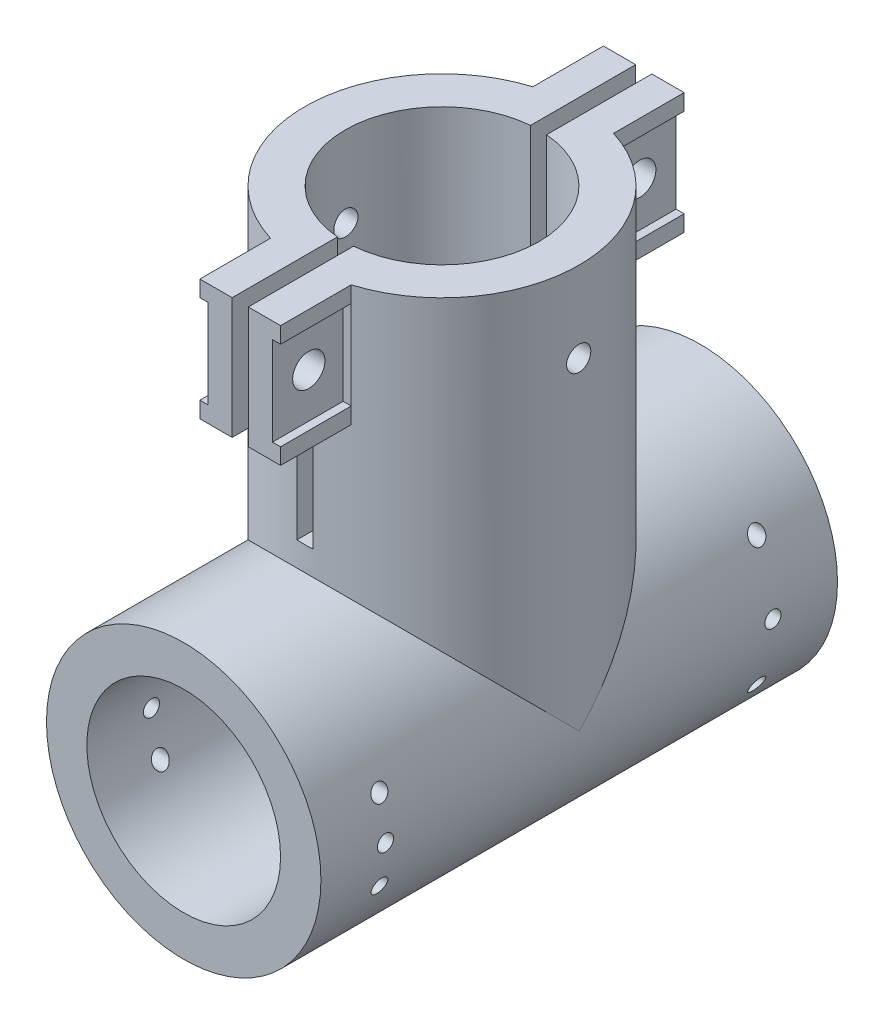
SolidWorks part; units mm, degrees
ref_plane "Front Plane" through (0, 0, 0) normal (0, 0, 1) x (1, 0, 0)
ref_plane "Top Plane" through (0, 0, 0) normal (0, 1, 0) x (1, 0, 0)
ref_plane "Right Plane" through (0, 0, 0) normal (1, 0, 0) x (0, 0, -1)
sketch "Sketch1" plane through (0, 0, 0) normal (0, 0, 1) x (1, 0, 0)
  circle A0 centre (-32.2971, 4.4232) radius 17
  circle A1 centre (-32.2971, 4.4232) radius 12
  dimension "D1" = 34
  dimension "D2" = 5
extrude "Boss-Extrude1" add sketch "Sketch1" along normal blind 64
ref_axis "Axis2" through (-32.2971, 4.4232, 64) along (0, 0, -1)
ref_plane "Plane1" through (0, 4.4232, 0) normal (0, 1, 0) x (1, 0, 0)
sketch "Sketch2" plane through (0, 4.4232, 0) normal (0, 1, 0) x (1, 0, 0)
  line L0 (-32.2971, -64) -> (-32.2971, 0) construction
  line L1 (-15.2971, 0) -> (-49.2971, 0) construction
  circle A0 centre (-32.2971, -32) radius 17
  circle A1 centre (-32.2971, -32) radius 12
  dimension "D1" = 32
  dimension "D2" = 5
  dimension "D3" = 34
extrude "Boss-Extrude2" add sketch "Sketch2" along normal blind 50
sketch "Sketch3" plane through (0, 0, 64) normal (0, 0, 1) x (1, 0, 0)
  circle A0 centre (-32.2971, 4.4232) radius 12
extrude "Cut-Extrude1" cut sketch "Sketch3" against normal through all
sketch "Sketch6" plane through (0, 54.4232, 0) normal (0, 1, 0) x (1, 0, 0)
  circle A0 centre (-32.2971, -32) radius 12
ref_axis "Axis3" through (-32.2971, 54.4232, 32) along (0, -1, 0)
ref_plane "Plane2" through (0, 0, 32) normal (0, 0, -1) x (-1, 0, 0)
sketch "Sketch4" plane through (0, 0, 32) normal (0, 0, -1) x (-1, 0, 0)
  line L0 (49.2971, 54.4232) -> (15.2971, 54.4232) construction
  line L1 (37.2971, 54.4232) -> (27.2971, 54.4232)
  line L2 (37.2971, 54.4232) -> (37.2971, 39.4232)
  line L3 (37.2971, 39.4232) -> (27.2971, 39.4232)
  line L4 (27.2971, 54.4232) -> (27.2971, 39.4232)
  line L5 (32.2971, 54.4232) -> (32.2971, 15.582) construction
  dimension "D1" = 10
  dimension "D2" = 5
  dimension "D3" = 15
extrude "Boss-Extrude3" add sketch "Sketch4" along normal mid plane 50
sketch "Sketch5" plane through (0, 0, 57) normal (0, 0, 1) x (1, 0, 0)
  line L0 (-37.2971, 54.4232) -> (-27.2971, 54.4232) construction
  line L1 (-33.2971, 54.4232) -> (-31.2971, 54.4232)
  line L2 (-33.2971, 54.4232) -> (-33.2971, 24.4232)
  line L3 (-33.2971, 24.4232) -> (-31.2971, 24.4232)
  line L4 (-31.2971, 54.4232) -> (-31.2971, 24.4232)
  line L5 (-32.2971, 54.4232) -> (-32.2971, 15.582) construction
  dimension "D1" = 2
  dimension "D2" = 1
  dimension "D3" = 30
extrude "Cut-Extrude2" cut sketch "Sketch5" against normal blind 50
extrude "Cut-Extrude3" cut sketch "Sketch6" against normal blind 50
sketch "Sketch7" plane through (-27.2971, 0, 0) normal (1, 0, 0) x (0, 0, -1)
  line L0 (-57, 54.4232) -> (-57, 39.4232) construction
  line L1 (-57, 52.4232) -> (-48.2481, 52.4232)
  line L2 (-57, 52.4232) -> (-57, 41.4232)
  line L3 (-57, 41.4232) -> (-48.2481, 41.4232)
  line L4 (-48.2481, 52.4232) -> (-48.2481, 41.4232)
  line L5 (-48.2481, 39.4232) -> (-48.2481, 54.4232) construction
  line L6 (-15.7519, 54.4232) -> (-15.7519, 39.4232) construction
  line L7 (-15.7519, 52.4232) -> (-7, 52.4232)
  line L8 (-15.7519, 52.4232) -> (-15.7519, 41.4232)
  line L9 (-15.7519, 41.4232) -> (-7, 41.4232)
  line L10 (-7, 52.4232) -> (-7, 41.4232)
  line L11 (-7, 54.4232) -> (-7, 39.4232) construction
  line L12 (-48.2481, 54.4232) -> (-57, 54.4232) construction
  line L13 (-48.2481, 39.4232) -> (-57, 39.4232) construction
  line L14 (-7, 54.4232) -> (-15.7519, 54.4232) construction
  line L15 (-7, 39.4232) -> (-15.7519, 39.4232) construction
  dimension "D1" = 2
  dimension "D2" = 2
  dimension "D3" = 2
  dimension "D4" = 2
extrude "Kes-Ekstrüzyon4" cut sketch "Sketch7" against normal blind 1
sketch "Sketch8" plane through (-28.2971, 0, 0) normal (1, 0, 0) x (0, 0, -1)
  line L0 (-7, 54.4232) -> (-15.7519, 54.4232) construction
  line L1 (-57, 52.4232) -> (-57, 41.4232) construction
  line L4 (-7, 41.4232) -> (-7, 52.4232) construction
  line L5 (-43.9583, 54.4232) -> (-57, 54.4232) construction
  circle A0 centre (-52.5, 46.9232) radius 2
  circle A1 centre (-11.5, 46.9232) radius 2
  point P6 (-57, 46.9232)
  dimension "D1" = 4
  dimension "D2" = 4
  dimension "D3" = 4.5
  dimension "D4" = 4.5
  dimension "D5" = 7.5
  dimension "D6" = 7.5
extrude "Cut-Extrude5" cut sketch "Sketch8" against normal through all
ref_plane "Plane3" through (-15.2971, 0, 0) normal (1, 0, 0) x (0, 0, -1)
sketch "Sketch9" plane through (-15.2971, 0, 0) normal (1, 0, 0) x (0, 0, -1)
  line L0 (35.2, 4.4232) -> (-35.2, 4.4232) construction
  line L1 (-64, 4.4232) -> (0, 4.4232) construction
  line L2 (-64, 21.4232) -> (-64, -12.5768) construction
  line L3 (0, -12.5768) -> (0, 21.4232) construction
  line L4 (-32, -27.5) -> (-32, 27.5) construction
  line L5 (-15.7519, 54.4232) -> (-48.2481, 54.4232) construction
  circle A0 centre (-56, 4.4232) radius 1
  circle A1 centre (-56, 9.4232) radius 1
  circle A2 centre (-56, -0.5768) radius 1
  circle A3 centre (-8, 4.4232) radius 1
  circle A4 centre (-8, 12.4232) radius 1
  circle A5 centre (-8, -3.5768) radius 1
  circle A6 centre (-32, 44.4232) radius 1.5
  dimension "D1" = 2
  dimension "D2" = 2
  dimension "D3" = 2
  dimension "D4" = 2
  dimension "D5" = 2
  dimension "D6" = 2
  dimension "D7" = 5
  dimension "D8" = 5
  dimension "D9" = 8
  dimension "D10" = 8
  dimension "D11" = 8
  dimension "D13" = 8
  dimension "D14" = 3
  dimension "D15" = 10
  dimension "D12" = 8
extrude "Cut-Extrude6" cut sketch "Sketch9" against normal through all
sketch "Sketch10" plane through (-37.2971, 0, 0) normal (-1, 0, 0) x (0, 0, 1)
  line L0 (15.7519, 51.4232) -> (9.7519, 51.4232)
  line L1 (15.7519, 39.4232) -> (15.7519, 54.4232) construction
  line L2 (7, 39.4232) -> (7, 54.4232) construction
  line L3 (7, 51.4232) -> (7, 42.4232)
  line L4 (9.7519, 42.4232) -> (15.7519, 42.4232)
  line L5 (9.7519, 50.0997) -> (9.7519, 51.4232)
  line L6 (15.125, 44.8303) -> (15.125, 49.0161)
  line L7 (15.125, 49.0161) -> (11.5, 51.109)
  line L8 (11.5, 51.109) -> (9.7519, 50.0997)
  line L9 (15.7519, 52.4232) -> (15.7519, 51.4232)
  line L10 (9.7519, 43.7467) -> (11.5, 42.7374)
  line L11 (11.5, 42.7374) -> (15.125, 44.8303)
  line L12 (9.7519, 43.7467) -> (9.7519, 42.4232)
  line L13 (15.7519, 41.4232) -> (7, 41.4232)
  line L14 (15.7519, 52.4232) -> (7, 52.4232)
  line L15 (7, 54.4232) -> (15.7519, 54.4232) construction
  line L16 (7, 39.4232) -> (15.7519, 39.4232) construction
  line L17 (7, 42.4232) -> (7, 41.4232)
  line L18 (7, 52.4232) -> (7, 51.4232)
  line L19 (7.875, 46.9232) -> (7.875, 44.9232) [skipped]
  line L20 (15.7519, 42.4232) -> (15.7519, 41.4232)
  line L21 (32, 54.4232) -> (32, -12.5768) construction
  line L22 (48.2481, 54.4232) -> (15.7519, 54.4232) construction
  line L23 (0, -12.5768) -> (64, -12.5768) construction
  line L24 (48.2481, 42.4232) -> (48.2481, 41.4232)
  line L25 (57, 52.4232) -> (57, 51.4232)
  line L26 (57, 42.4232) -> (57, 41.4232)
  line L27 (48.2481, 52.4232) -> (57, 52.4232)
  line L28 (48.2481, 41.4232) -> (57, 41.4232)
  line L29 (54.2481, 43.7467) -> (54.2481, 42.4232)
  line L30 (52.5, 42.7374) -> (48.875, 44.8303)
  line L31 (54.2481, 43.7467) -> (52.5, 42.7374)
  line L32 (48.2481, 52.4232) -> (48.2481, 51.4232)
  line L33 (52.5, 51.109) -> (54.2481, 50.0997)
  line L34 (48.875, 49.0161) -> (52.5, 51.109)
  line L35 (48.875, 44.8303) -> (48.875, 49.0161)
  line L36 (54.2481, 50.0997) -> (54.2481, 51.4232)
  line L37 (54.2481, 42.4232) -> (48.2481, 42.4232)
  line L38 (57, 51.4232) -> (57, 42.4232)
  line L39 (48.2481, 51.4232) -> (54.2481, 51.4232)
  circle A0 centre (11.5, 46.9232) radius 3.625 construction
  circle A1 centre (52.5, 46.9232) radius 3.625 construction
  point P13 (15.7519, 41.9232)
  dimension "D1" = 7.25
  dimension "D2" = 180
  dimension "D3" = 2
  dimension "D4" = 1
  dimension "D5" = 2
  dimension "D6" = 1
  dimension "D7" = 6
extrude "Cut-Extrude7" cut sketch "Sketch10" against normal blind 1
